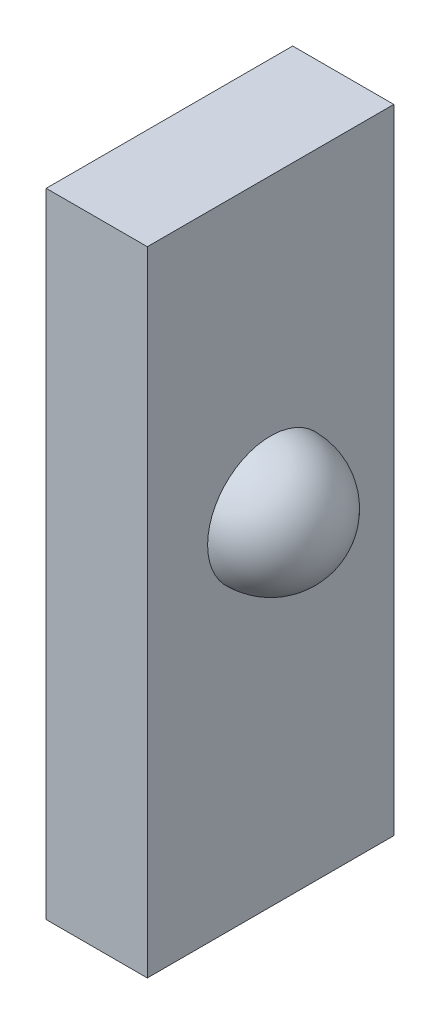
SolidWorks part; units mm, degrees
ref_plane "前视基准面" through (0, 0, 0) normal (0, 0, 1) x (1, 0, 0)
ref_plane "上视基准面" through (0, 0, 0) normal (0, 1, 0) x (1, 0, 0)
ref_plane "右视基准面" through (0, 0, 0) normal (1, 0, 0) x (0, 0, -1)
other "Configuration Table"
sketch "草图1" plane through (0, 0, 0) normal (1, 0, 0) x (0, 0, -1)
  line L0 (0, 5.1094) -> (0, -5.1094)
  arc A0 (0, -5.1094) -> (0, 5.1094) centre (0, 0) ccw
  point P1 (0, 10.4487)
  point P5 (0, 7.0531)
  point P6 (0, 5.1094)
revolve "旋转1" add sketch "草图1" angle 180 about L0
sketch "草图5" plane through (0, 0, 0) normal (0, 0, 1) x (1, 0, 0)
  line L1 (-8.2072, 23.408) -> (0, 23.408)
  line L2 (-8.2072, 23.408) -> (-8.2072, -27.9806)
  line L3 (-8.2072, -27.9806) -> (0, -27.9806)
  line L4 (0, 23.408) -> (0, -27.9806)
extrude "凸台-拉伸1" add sketch "草图5" along normal blind 10 and the other way blind 10
sketch "草图7" plane through (0, 0, 0) normal (0, 0, 1) x (1, 0, 0)
  line L0 (-8.2072, 23.408) -> (-8.2072, -27.9806) construction
  line L1 (-8.2072, 2.9275) -> (-8.2072, -7.5001)
  arc A0 (-8.2072, 2.9275) -> (-8.2072, -7.5001) centre (-8.2072, -2.2863) ccw
revolve "切除-旋转1" cut sketch "草图7" angle 360 about L1
pattern_linear "阵列(线性)1" count 2 spacing 15 along (0, 1, 0) count 2 spacing 15 along (0, -1, 0) of "切除-旋转1" pattern seed only yes
